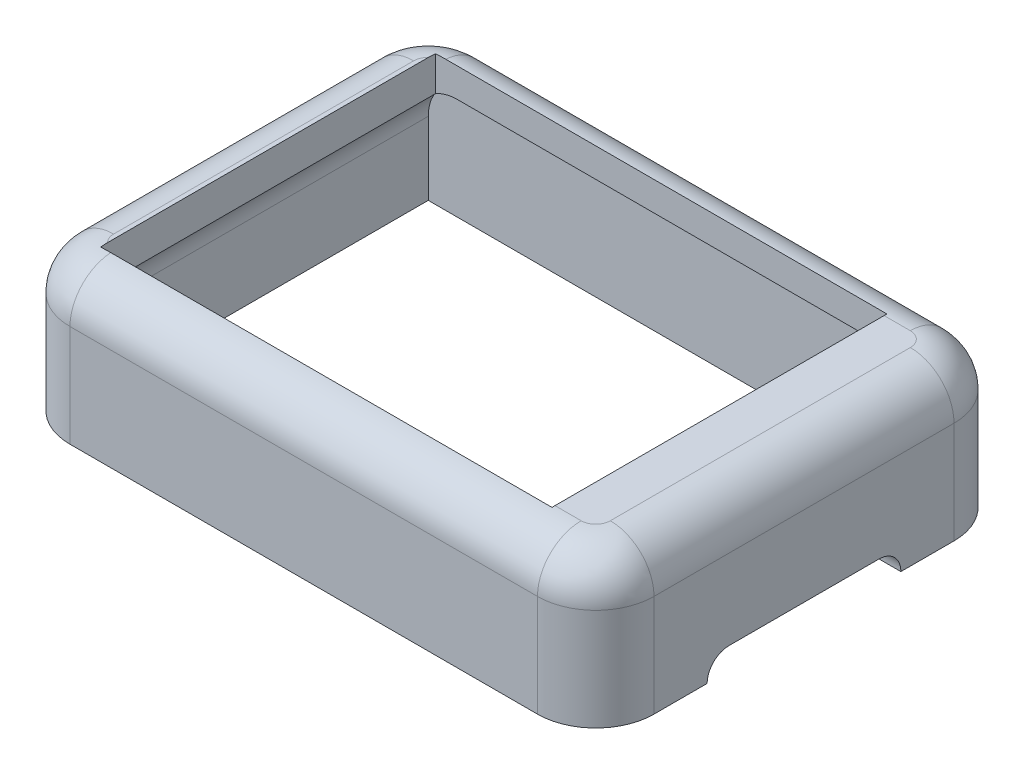
SolidWorks part; units mm, degrees
ref_plane "Front Plane" through (0, 0, 0) normal (0, 0, 1) x (1, 0, 0)
ref_plane "Top Plane" through (0, 0, 0) normal (0, 1, 0) x (1, 0, 0)
ref_plane "Right Plane" through (0, 0, 0) normal (1, 0, 0) x (0, 0, -1)
sketch "Sketch1" plane through (0, 0, 0) normal (0, 1, 0) x (1, 0, 0)
  line L1 (-20.05, -14.3) -> (20.05, -14.3)
  line L2 (-20.05, -14.3) -> (-20.05, 14.3)
  line L3 (-20.05, 14.3) -> (20.05, 14.3)
  line L4 (20.05, -14.3) -> (20.05, 14.3)
  line L5 (-20.05, -14.3) -> (20.05, 14.3) construction
  line L6 (-20.05, 14.3) -> (20.05, -14.3) construction
  line L7 (18.25, -12.5) -> (-18.25, -12.5)
  line L8 (18.25, -12.5) -> (18.25, 12.5)
  line L9 (18.25, 12.5) -> (-18.25, 12.5)
  line L10 (-18.25, -12.5) -> (-18.25, 12.5)
  line L11 (18.25, -12.5) -> (-18.25, 12.5) construction
  line L12 (18.25, 12.5) -> (-18.25, -12.5) construction
  point P0 (0, 0)
  point P5 (0, 0)
  dimension "D1" = 1.8
  dimension "D2" = 1.8
  dimension "D3" = 25
  dimension "D4" = 36.5
extrude "Boss-Extrude1" add sketch "Sketch1" along normal blind 8
sketch "Sketch2" plane through (0, 8, 0) normal (0, 1, 0) x (1, 0, 0)
  line L0 (-18.25, 0) -> (18.25, 0) construction
  line L1 (20.05, -14.3) -> (-20.05, -14.3)
  line L2 (20.05, -14.3) -> (20.05, 14.3)
  line L3 (20.05, 14.3) -> (-20.05, 14.3)
  line L4 (-20.05, -14.3) -> (-20.05, 14.3)
  line L5 (20.05, -14.3) -> (-20.05, 14.3) construction
  line L6 (20.05, 14.3) -> (-20.05, -14.3) construction
  line L7 (-18.25, 12.5) -> (-18.25, -12.5) construction
  line L8 (18.25, -12.5) -> (18.25, 12.5) construction
  line L10 (14.25, -11.5) -> (-16.75, -11.5)
  line L11 (14.25, -11.5) -> (14.25, 11.5)
  line L12 (14.25, 11.5) -> (-16.75, 11.5)
  line L13 (-16.75, -11.5) -> (-16.75, 11.5)
  line L14 (14.25, -11.5) -> (-16.75, 11.5) construction
  line L15 (14.25, 11.5) -> (-16.75, -11.5) construction
  point P0 (0, 0)
  point P13 (-1.25, 0)
  dimension "D1" = 23
  dimension "D2" = 31
  dimension "D3" = 1.5
extrude "Boss-Extrude2" add sketch "Sketch2" along normal blind 2
fillet "Fillet1" radius 4 4 edges at (-20.05, 5, -14.3) (20.05, 5, -14.3) (20.05, 5, 14.3) (-20.05, 5, 14.3)
fillet "Fillet4" radius 3 8 edges at (-20.05, 10, 0) (-18.8784, 10, -13.1284) (0, 10, -14.3) (18.8784, 10, -13.1284) (20.05, 10, 0) (18.8784, 10, 13.1284) (0, 10, 14.3) (-18.8784, 10, 13.1284)
fillet "Fillet5" radius 3 2 edges at (-18.25, 8, 0) (18.25, 8, 0)
sketch "Sketch3" plane through (20.05, 0, 0) normal (1, 0, 0) x (0, 0, -1)
  line L0 (-10.3, 0) -> (0, 0) construction
  line L1 (0, 0) -> (10.3, 0) construction
  line L2 (-5.15, 0) -> (-5.15, 7) construction
  line L3 (10.3, 7) -> (-10.3, 7) construction
  line L4 (5.15, 0) -> (-5.15, 0) construction
  line L5 (5.15, -1.5) -> (-5.15, -1.5)
  line L6 (5.15, 1.5) -> (-5.15, 1.5)
  arc A0 (5.15, -1.5) -> (5.15, 1.5) centre (5.15, 0) ccw
  arc A1 (-5.15, 1.5) -> (-5.15, -1.5) centre (-5.15, 0) ccw
  point P11 (0, 0)
  dimension "D1" = 1.5
extrude "Cut-Extrude1" cut sketch "Sketch3" against normal up to next
